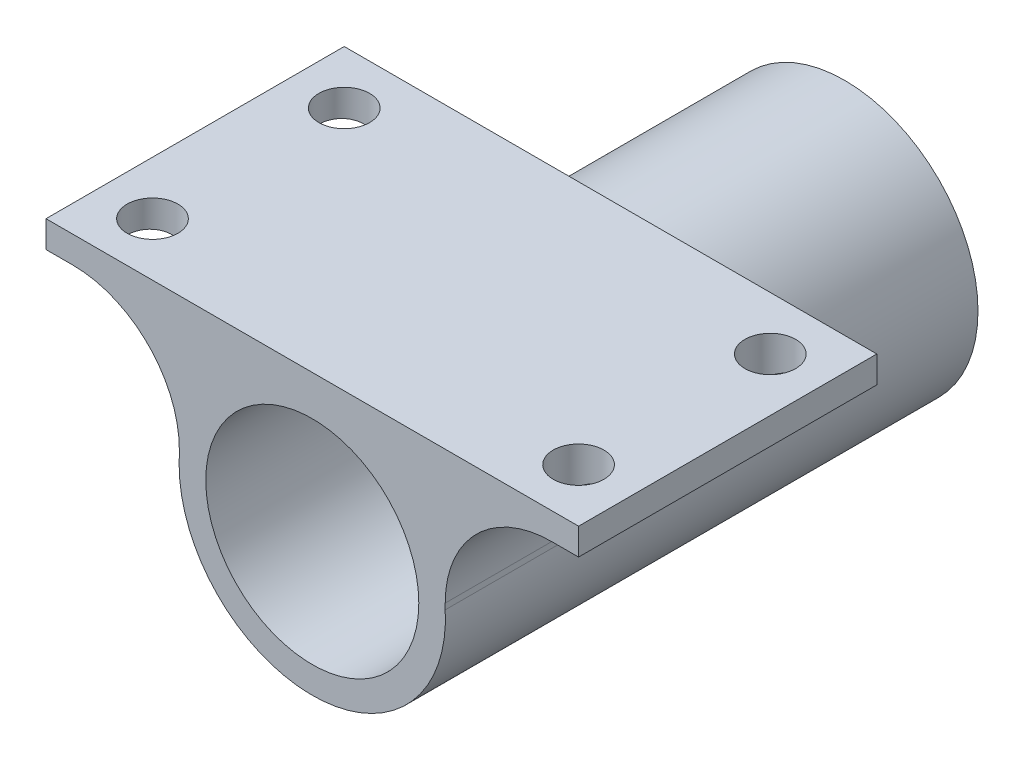
SolidWorks part; units mm, degrees
ref_plane "Front" through (0, 0, 0) normal (0, 0, 1) x (1, 0, 0)
ref_plane "Top" through (0, 0, 0) normal (0, 1, 0) x (1, 0, 0)
ref_plane "Right" through (0, 0, 0) normal (1, 0, 0) x (0, 0, -1)
sketch "Sketch1" plane through (0, 0, 0) normal (0, 0, 1) x (1, 0, 0)
  line L2 (-25, 11.2434) -> (-25, 13.7566)
  line L3 (-25, 13.7566) -> (25, 13.7566)
  line L4 (25, 11.2434) -> (25, 13.7566)
  line L5 (0, 12.5) -> (-25, 12.5) construction
  line L6 (0, 12.5) -> (25, 12.5) construction
  line L7 (25, 11.2434) -> (22.4809, 11.2434)
  line L8 (12.4809, 1.2434) -> (12.4809, 0.6908)
  line L9 (-12.4809, 0.6908) -> (-12.4809, 1.2434)
  line L10 (-22.4809, 11.2434) -> (-25, 11.2434)
  circle A0 centre (0, 0) radius 10
  arc A1 (-12.4809, 0.6908) -> (12.4809, 0.6908) centre (0, 0) ccw
  arc A4 (22.4809, 11.2434) -> (12.4809, 1.2434) centre (22.4809, 1.2434) ccw
  arc A5 (-12.4809, 1.2434) -> (-22.4809, 11.2434) centre (-22.4809, 1.2434) ccw
  point P4 (0, 12.5)
  point P12 (5.4623, 11.2434)
  dimension "D1" = 20
  dimension "D2" = 25
  dimension "D4" = 10
  dimension "D3" = 50
extrude "Boss-Extrude1" add sketch "Sketch1" along normal blind 48
sketch "Sketch3" plane through (0, 0, 0) normal (0, 0, -1) x (-1, 0, 0)
  line L0 (-7.5, 0) -> (7.5, 0) construction
  circle A0 centre (0, 0) radius 3.5
  circle A1 centre (0, 0) radius 12.5
  circle A2 centre (7.5, 0) radius 0.95
  circle A3 centre (-7.5, 0) radius 0.95
  dimension "D1" = 7
  dimension "D2" = 25
  dimension "D3" = 1.9
  dimension "D4" = 1.9
  dimension "D5" = 7.5
  dimension "D6" = 7.5
extrude "Boss-Extrude3" add sketch "Sketch3" along normal blind 2
sketch "Sketch4" plane through (0, 13.7566, 0) normal (0, 1, 0) x (1, 0, 0)
  line L0 (25, -48) -> (25, 0) construction
  line L2 (-25, -48) -> (-25, 0) construction
  line L3 (25, -48) -> (-25, -48) construction
  circle A0 centre (-20, -25) radius 2.3813
  circle A1 centre (20, -25) radius 2.3813
  circle A2 centre (20, -43) radius 2.3813
  circle A3 centre (-20, -43) radius 2.3813
  dimension "D2" = 18
  dimension "D3" = 4.7625
  dimension "D4" = 18
  dimension "D5" = 5
  dimension "D7" = 5
  dimension "D9" = 5
  dimension "D10" = 5
  dimension "D11" = 5
  dimension "D12" = 5
extrude "Cut-Extrude1" cut sketch "Sketch4" against normal through all
sketch "Sketch6" plane through (0, 0, -2) normal (0, 0, -1) x (-1, 0, 0)
  line L0 (10.178, -7.2566) -> (29.1547, -20.7862) construction
  line L1 (-29.1547, 20.7862) -> (29.1547, 20.7862)
  line L2 (-29.1547, 20.7862) -> (-29.1547, -20.7862)
  line L3 (-29.1547, -20.7862) -> (29.1547, -20.7862)
  line L4 (29.1547, 20.7862) -> (29.1547, -20.7862)
  line L5 (-29.1547, 20.7862) -> (-10.178, 7.2566) construction
  line L6 (-29.1547, -20.7862) -> (-10.178, -7.2566) construction
  line L7 (10.178, 7.2566) -> (29.1547, 20.7862) construction
  circle A0 centre (0, 0) radius 12.5
  dimension "D1" = 25
extrude "Cut-Extrude4" cut sketch "Sketch6" against normal blind 22
